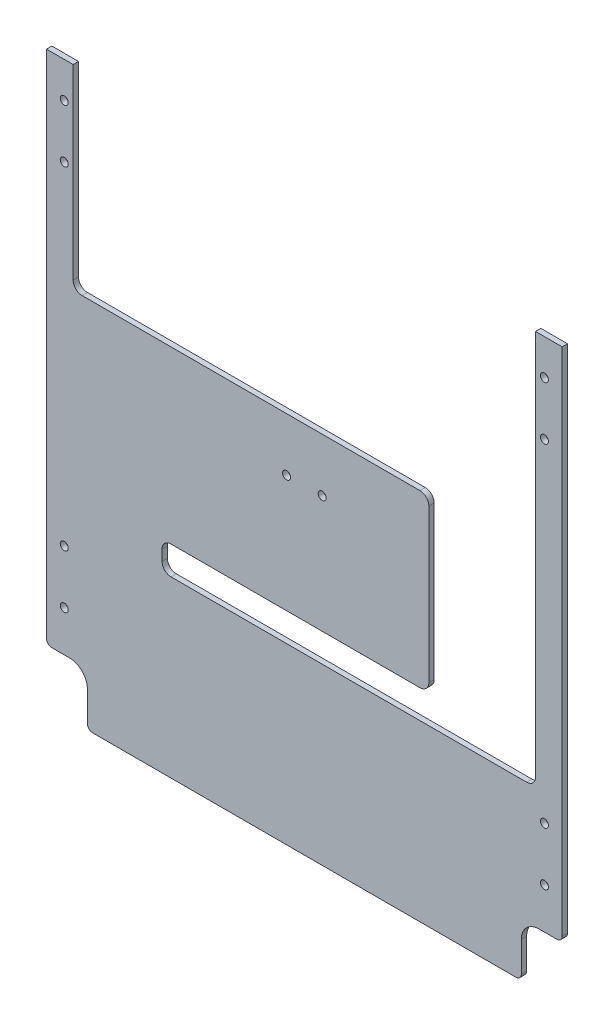
SolidWorks part; units mm, degrees
ref_plane "Front" through (0, 0, 0) normal (0, 0, 1) x (1, 0, 0)
ref_plane "Top" through (0, 0, 0) normal (0, 1, 0) x (1, 0, 0)
ref_plane "Right" through (0, 0, 0) normal (1, 0, 0) x (0, 0, -1)
sketch "Esquisse1" plane through (0, 0, 0) normal (0, 0, 1) x (1, 0, 0)
  line L1 (0, 0) -> (290, 0)
  line L2 (0, 0) -> (0, 320)
  line L3 (0, 320) -> (290, 320)
  line L4 (290, 0) -> (290, 320)
  dimension "D1" = 290
  dimension "D2" = 320
extrude "Boss.-Extru.1" add sketch "Esquisse1" along normal blind 3
sketch "Esquisse2" plane through (0, 0, 3) normal (0, 0, 1) x (1, 0, 0)
  line L0 (145, 0) -> (145, 56.1801) construction
  line L1 (290, 0) -> (267, 0)
  line L2 (290, 0) -> (290, 30)
  line L3 (290, 30) -> (267, 30)
  line L4 (267, 0) -> (267, 30)
  line L5 (0, 0) -> (290, 0) construction
  line L6 (23, 0) -> (23, 30)
  line L7 (0, 30) -> (23, 30)
  line L8 (0, 0) -> (0, 30)
  line L9 (0, 0) -> (23, 0)
  dimension "D1" = 23
  dimension "D2" = 30
extrude "Enlèv. mat.-Extru.1" cut sketch "Esquisse2" against normal through all both and the other way through all
fillet "Congé1" radius 10 2 edges at (267, 30, 1.5) (23, 30, 1.5)
fillet "Congé2" radius 3 4 edges at (290, 30, 1.5) (0, 30, 1.5) (23, 0, 1.5) (267, 0, 1.5)
sketch "Esquisse3" plane through (0, 0, 3) normal (0, 0, 1) x (1, 0, 0)
  line L0 (290, 320) -> (0, 320) construction
  line L1 (75, 320) -> (215, 320)
  line L2 (75, 320) -> (75, 210)
  line L3 (75, 210) -> (215, 210)
  line L4 (215, 320) -> (215, 210)
  line L5 (145, 210) -> (145, 0) construction
  line L6 (26, 0) -> (264, 0) construction
  dimension "D1" = 140
  dimension "D2" = 110
extrude "Enlèv. mat.-Extru.2" cut sketch "Esquisse3" against normal through all both and the other way through all
sketch "Esquisse4" plane through (0, 0, 3) normal (0, 0, 1) x (1, 0, 0)
  line L0 (290, 320) -> (215, 320) construction
  line L1 (215, 320) -> (275, 320)
  line L2 (215, 320) -> (215, 98)
  line L3 (215, 98) -> (275, 98)
  line L4 (275, 320) -> (275, 98)
  line L5 (290, 33) -> (290, 320) construction
  line L6 (215, 320) -> (215, 210) construction
  line L7 (26, 0) -> (264, 0) construction
  dimension "D1" = 15
  dimension "D2" = 98
extrude "Enlèv. mat.-Extru.3" cut sketch "Esquisse4" against normal through all both and the other way through all
sketch "Esquisse5" plane through (0, 0, 3) normal (0, 0, 1) x (1, 0, 0)
  line L0 (75, 320) -> (0, 320) construction
  line L1 (75, 210) -> (15, 210)
  line L2 (75, 210) -> (75, 320)
  line L3 (75, 320) -> (15, 320)
  line L4 (15, 210) -> (15, 320)
  line L5 (0, 320) -> (0, 33) construction
  dimension "D1" = 15
extrude "Enlèv. mat.-Extru.4" cut sketch "Esquisse5" against normal through all both and the other way through all
sketch "Esquisse6" plane through (0, 0, 3) normal (0, 0, 1) x (1, 0, 0)
  line L0 (215, 98) -> (215, 210) construction
  line L1 (215, 98) -> (65, 98)
  line L2 (215, 98) -> (215, 114)
  line L3 (215, 114) -> (65, 114)
  line L4 (65, 98) -> (65, 114)
  line L5 (26, 0) -> (264, 0) construction
  line L6 (0, 320) -> (0, 33) construction
  dimension "D1" = 16
  dimension "D2" = 98
  dimension "D3" = 65
extrude "Enlèv. mat.-Extru.5" cut sketch "Esquisse6" against normal through all both and the other way through all
fillet "Congé3" radius 5 6 edges at (275, 98, 1.5) (65, 98, 1.5) (65, 114, 1.5) (215, 114, 1.5) (215, 210, 1.5) (15, 210, 1.5)
sketch "Esquisse7" plane through (0, 0, 3) normal (0, 0, 1) x (1, 0, 0)
  line L0 (280, 320) -> (280, 300) construction
  line L1 (290, 320) -> (275, 320) construction
  line L2 (275, 320) -> (275, 103) construction
  line L3 (280, 300) -> (280, 270) construction
  line L4 (145, 0) -> (145, 300) construction
  line L5 (26, 0) -> (264, 0) construction
  line L6 (10, 300) -> (10, 270) construction
  line L7 (10, 320) -> (10, 300) construction
  line L8 (0, 176.5) -> (290, 176.5) construction
  line L9 (0, 320) -> (0, 33) construction
  line L10 (290, 33) -> (290, 320) construction
  line L11 (280, 53) -> (280, 83) construction
  line L12 (280, 33) -> (280, 53) construction
  line L13 (10, 33) -> (10, 53) construction
  line L14 (10, 53) -> (10, 83) construction
  circle A0 centre (280, 300) radius 2.25
  circle A1 centre (280, 270) radius 2.25
  circle A2 centre (10, 270) radius 2.25
  circle A3 centre (10, 300) radius 2.25
  circle A4 centre (280, 83) radius 2.25
  circle A5 centre (280, 53) radius 2.25
  circle A6 centre (10, 53) radius 2.25
  circle A7 centre (10, 83) radius 2.25
  dimension "D2" = 4.5
  dimension "D4" = 30
  dimension "D1" = 5
  dimension "D3" = 20
extrude "Enlèv. mat.-Extru.6" cut sketch "Esquisse7" against normal through all both and the other way through all
sketch "Esquisse8" plane through (0, 0, 3) normal (0, 0, 1) x (1, 0, 0)
  line L0 (145, 0) -> (145, 158.346) construction
  line L1 (26, 0) -> (264, 0) construction
  line L2 (210, 210) -> (20, 210) construction
  circle A0 centre (135, 180) radius 2.25
  circle A1 centre (155, 180) radius 2.25
  dimension "D1" = 4.5
  dimension "D2" = 20
  dimension "D3" = 30
extrude "Enlèv. mat.-Extru.7" cut sketch "Esquisse8" against normal through all both and the other way through all
